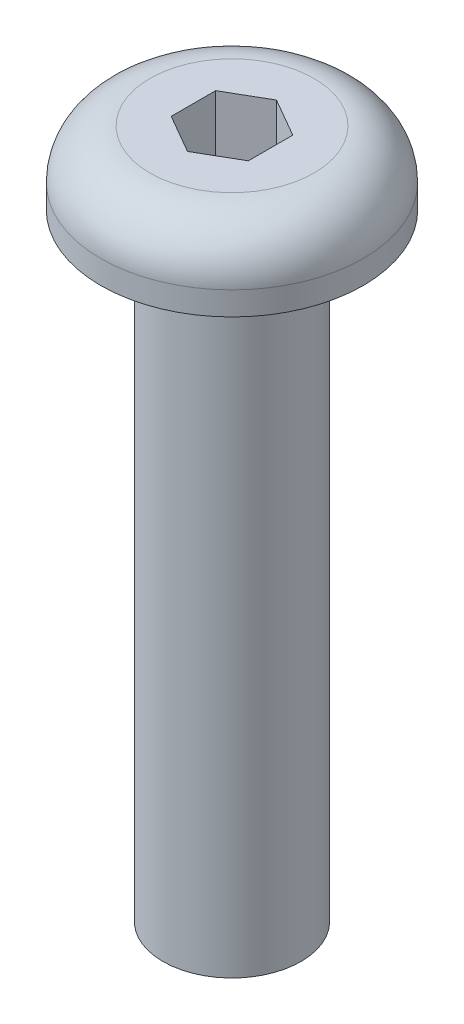
SolidWorks part; units mm, degrees
ref_plane "Front Plane" through (0, 0, 0) normal (0, 0, 1) x (1, 0, 0)
ref_plane "Top Plane" through (0, 0, 0) normal (0, 1, 0) x (1, 0, 0)
ref_plane "Right Plane" through (0, 0, 0) normal (1, 0, 0) x (0, 0, -1)
sketch "Sketch1" plane through (0, 0, 0) normal (0, 1, 0) x (1, 0, 0)
  circle A0 centre (0, 0) radius 1.4224
  dimension "D1" = 2.8448
extrude "Boss-Extrude1" add sketch "Sketch1" along normal blind 12.7
sketch "Sketch2" plane through (0, 12.7, 0) normal (0, 1, 0) x (1, 0, 0)
  circle A0 centre (0, 0) radius 2.7051
  dimension "D1" = 5.4102
extrude "Boss-Extrude2" add sketch "Sketch2" along normal blind 1.4986
fillet "Fillet1" radius 1.016 1 edges at (0, 14.1986, 2.7051)
sketch "Sketch3" plane through (0, 14.1986, 0) normal (0, 1, 0) x (1, 0, 0)
  line L1 (0, 0.9165) -> (-0.7937, 0.4583)
  line L2 (-0.7937, 0.4583) -> (-0.7937, -0.4583)
  line L3 (-0.7937, -0.4583) -> (0, -0.9165)
  line L4 (0, -0.9165) -> (0.7938, -0.4583)
  line L5 (0.7938, -0.4583) -> (0.7938, 0.4583)
  line L6 (0.7938, 0.4583) -> (0, 0.9165)
  circle A0 centre (0, 0) radius 0.7937 construction
  dimension "D1" = 1.5875
extrude "Cut-Extrude1" cut sketch "Sketch3" against normal blind 2.3813
